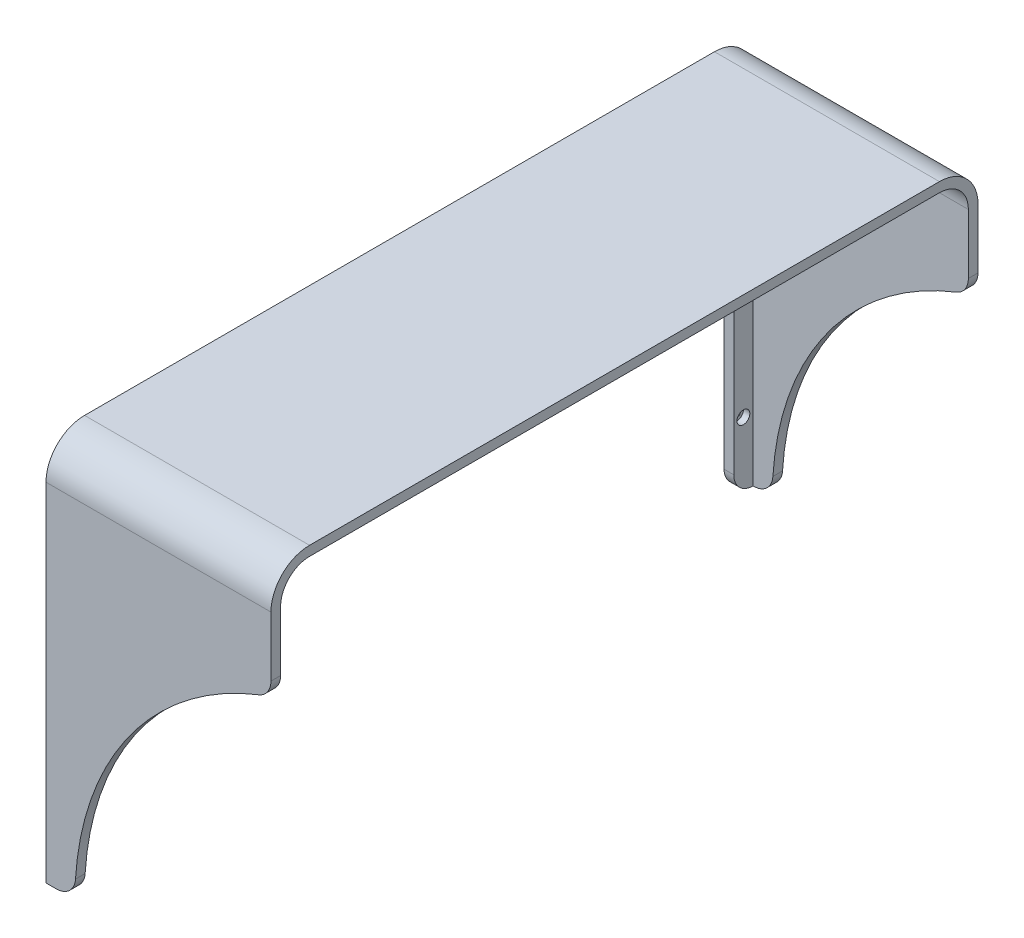
SolidWorks part; units mm, degrees
material "6061 Alloy"
ref_plane "Front Plane" through (0, 0, 0) normal (0, 0, 1) x (1, 0, 0)
ref_plane "Top Plane" through (0, 0, 0) normal (0, 1, 0) x (1, 0, 0)
ref_plane "Right Plane" through (0, 0, 0) normal (1, 0, 0) x (0, 0, -1)
sketch "Sketch1" plane through (0, 0, 0) normal (1, 0, 0) x (0, 0, -1)
  line L0 (-107, 57) -> (107, 57)
  line L1 (-110, 60) -> (110, 60)
  line L2 (-110, 60) -> (-110, -60)
  line L3 (-110, -60) -> (-101, -60)
  line L4 (110, 60) -> (110, -60)
  line L5 (107, 57) -> (107, -60)
  line L7 (-107, 57) -> (-107, -60)
  line L8 (-101, 51) -> (-101, -60)
  line L10 (101, 51) -> (101, -60)
  line L11 (-101, 51) -> (101, 51)
  line L12 (-107, 57) -> (-107, -57) construction
  line L13 (-101, 51) -> (-101, -51) construction
  line L14 (101, 51) -> (101, -51) construction
  line L15 (107, 57) -> (107, -57) construction
  line L16 (-101, -51) -> (101, -51) construction
  line L18 (-107, -57) -> (107, -57) construction
  line L19 (101, -60) -> (110, -60)
  line L20 (-110, -60) -> (110, -60) construction
  point P0 (0, 0)
  dimension "D1" = 220
  dimension "D2" = 120
  dimension "D3" = 60
  dimension "D4" = 110
  dimension "D5" = 3
  dimension "D6" = 6
extrude "Boss-Extrude1" add sketch "Sketch1" along normal blind 70 contours L5 L19 L4 L1 L2 L3 L7 L0 region at (0, -1.5, 109.506)
extrude "Boss-Extrude2" add sketch "Sketch1<3>" along normal blind 3 contours L10 L19 L5 L0 L7 L3 L8 L11 region at (0, 54.561, 0)
sketch "Sketch1<3>" plane through (0, 0, 0) normal (1, 0, 0) x (0, 0, -1) same geometry as "Sketch1"
sketch "Sketch2" plane through (0, 0, 110) normal (0, 0, 1) x (1, 0, 0)
  circle A0 centre (99, -60) radius 90
  point P2 (0, 0)
  dimension "D1" = 180
  dimension "D2" = 99
extrude "Cut-Extrude1" cut sketch "Sketch2" against normal through all
fillet "Fillet2" radius 9 2 edges at (36.5, 57, -107) (36.5, 57, 107)
fillet "Fillet3" radius 3 2 edges at (1.5, 51, -101) (1.5, 51, 101)
fillet "Fillet4" radius 12 2 edges at (35, 60, -110) (35, 60, 110)
fillet "Fillet5" radius 6 6 edges at (1.5, -60, 101) (9, -60, 108.5) (1.5, -60, -101) (9, -60, -108.5) (70, 25.1998, -108.5) (70, 25.1998, 108.5)
sketch "Sketch3" plane through (3, 0, 0) normal (1, 0, 0) x (0, 0, -1)
  line L0 (-101, 48) -> (-101, -54) construction
  line L1 (-98, 51) -> (98, 51) construction
  line L2 (101, 48) -> (101, -54) construction
  line L3 (-98, 60) -> (98, 60) construction
  line L4 (-110, 48) -> (-110, 29.3924) construction
  circle A0 centre (-104, -40) radius 2
  circle A1 centre (-104, 20) radius 2
  circle A2 centre (-70, 54) radius 2
  circle A3 centre (0, 54) radius 2
  circle A4 centre (70, 54) radius 2
  circle A5 centre (104, 20) radius 2
  circle A6 centre (104, -40) radius 2
  point P15 (0, 0)
  point P18 (0, 0)
  point P19 (0, 0)
  point P22 (0, 0)
  point P25 (0, 0)
  point P26 (0, 0)
  dimension "D2" = 4
  dimension "D3" = 3
  dimension "D4" = 3
  dimension "D1" = 3
  dimension "D5" = 40
  dimension "D6" = 60
  dimension "D7" = 110
  dimension "D8" = 70
  dimension "D9" = 70
extrude "Cut-Extrude2" cut sketch "Sketch3" against normal blind 2
sketch "Sketch4" plane through (3, 0, 0) normal (1, 0, 0) x (0, 0, -1)
  circle A0 centre (-104, -40) radius 1.1
  circle A1 centre (-104, 20) radius 1.1
  circle A2 centre (-70, 54) radius 1.1
  circle A3 centre (0, 54) radius 1.1
  circle A4 centre (70, 54) radius 1.1
  circle A5 centre (104, 20) radius 1.1
  circle A6 centre (104, -40) radius 1.1
  dimension "D1" = 2.2
extrude "Cut-Extrude3" cut sketch "Sketch4" against normal blind 3
